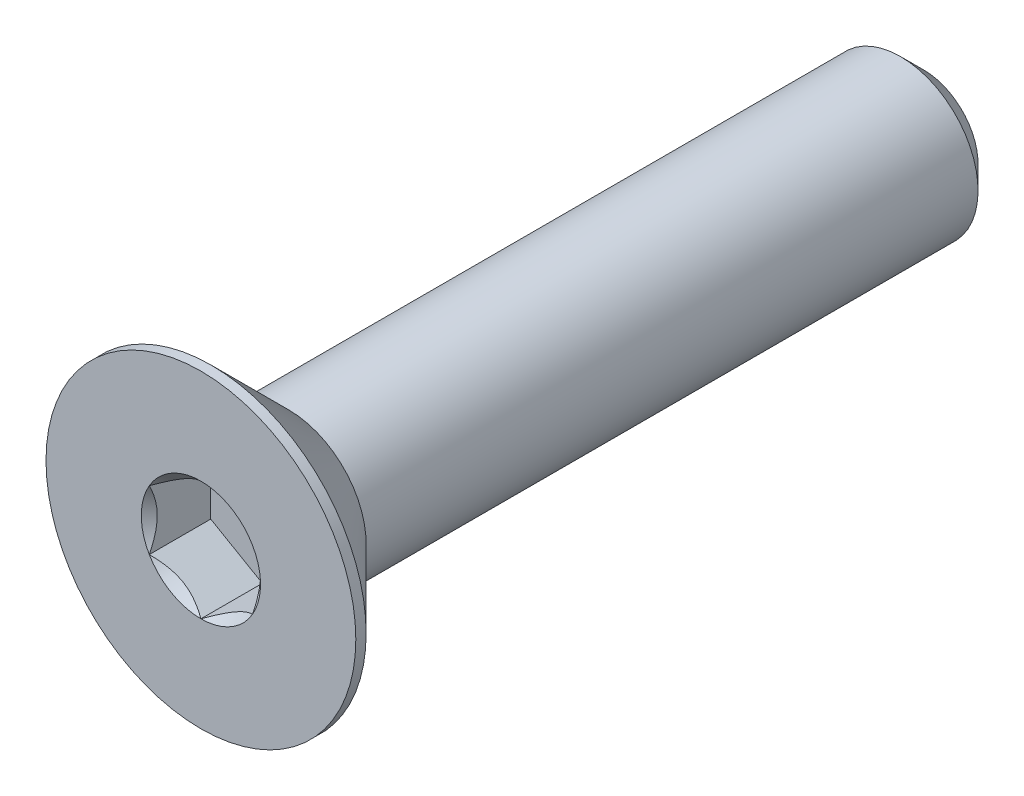
SolidWorks part; units mm, degrees
ref_plane "Front" through (0, 0, 0) normal (0, 0, 1) x (1, 0, 0)
ref_plane "Top" through (0, 0, 0) normal (0, 1, 0) x (1, 0, 0)
ref_plane "Right" through (0, 0, 0) normal (1, 0, 0) x (0, 0, -1)
sketch "Sketch1" plane through (0, 0, 0) normal (1, 0, 0) x (0, 0, -1)
  line L0 (-7, 3) -> (-6.8, 3) construction
  line L1 (-6.8, 3) -> (-5.3, 1.5) construction
  line L2 (-7, 1.5) -> (7, 1.5) construction
  line L3 (7, 1.5) -> (7, 0) construction
  line L4 (7, 0) -> (-7, 0) construction
  line L5 (-7, 0) -> (-7, 3) construction
  line L6 (-7, 3) -> (-7, -3) construction
  line L7 (7, 1.5) -> (7, -1.5) construction
  line L8 (-7, -3) -> (-6.8, -3) construction
  line L9 (-6.8, -3) -> (-5.3, -1.5) construction
  line L11 (-7, 1.5) -> (-7, 0) construction
  line L12 (-5.3, 1.5) -> (-5.3, 0) construction
  line L13 (6.9688, 1.5541) -> (7.2188, 1.1211) construction
  line L14 (7.2188, 1.1211) -> (7.4688, 1.5541) construction
  line L15 (7.4688, 1.5541) -> (6.9688, 1.5541) construction
  line L16 (7.2188, 1.5541) -> (7.2188, 1.5) construction
  line L17 (7.2188, 1.5) -> (7.2188, 1.1752) construction
  line L18 (7.2188, 1.1752) -> (7.2188, 1.1211) construction
  line L19 (7.2188, 1.5271) -> (7.4531, 1.5271) construction
  line L20 (7.2188, 1.5271) -> (6.9844, 1.5271) construction
  line L21 (7, 1.5) -> (7.4375, 1.5) construction
  line L22 (7.1875, 1.1752) -> (7.25, 1.1752) construction
  line L23 (7, -1.5) -> (-5.3, -1.5) construction
  point P10 (5.75, -1.5)
  point P24 (-5.3, 1.5)
  point P30 (0, 0)
  dimension "Head Diameter" = 6
  dimension "Head Height" = 1.7
  dimension "Length" = 14
  dimension "Countersink Angle" = 90
  dimension "Thread Pitch" = 0.5
  dimension "D2" = 0.0625
  dimension "Thread Size" = 3
  dimension "D1" = 1.25
sketch "Sketch2" plane through (0, 0, 0) normal (0, 0, 1) x (1, 0, 0)
  line L1 (0, 1.1547) -> (-1, 0.5774) construction
  line L2 (-1, 0.5774) -> (-1, -0.5774) construction
  line L3 (-1, -0.5774) -> (0, -1.1547) construction
  line L4 (0, -1.1547) -> (1, -0.5774) construction
  line L5 (1, -0.5774) -> (1, 0.5774) construction
  line L6 (1, 0.5774) -> (0, 1.1547) construction
  circle A0 centre (0, 0) radius 1 construction
  dimension "Drive Size" = 2
sketch "Sketch3" plane through (0, 0, 0) normal (1, 0, 0) x (0, 0, -1)
  line L0 (-7, 1.5) -> (7, 1.5)
  line L1 (7, 1.5) -> (7, 0)
  line L2 (7, 0) -> (-7, 0)
  line L3 (-7, 0) -> (-7, 1.5)
revolve "Revolve1" add sketch "Sketch3" angle 360 about L4
chamfer "Chamfer1" distance 0.45 angle 45 1 edges at (0, 1.5, -7)
sketch "Sketch6" plane through (0, 0, 0) normal (1, 0, 0) x (0, 0, -1)
  line L0 (-7, 3) -> (-6.8, 3)
  line L1 (-6.8, 3) -> (-5.3, 1.5)
  line L2 (-5.3, 1.5) -> (-5.3, 0)
  line L3 (-5.3, 0) -> (-7, 0)
  line L4 (-7, 0) -> (-7, 3)
revolve "Revolve2" add sketch "Sketch6" angle 360 about L4
sketch "Sketch8" plane through (0, 0, 7) normal (0, 0, 1) x (1, 0, 0)
  line L0 (0, 1.1547) -> (-1, 0.5774) construction
  line L1 (1, 0.5774) -> (0, 1.1547) construction
  line L2 (1, -0.5774) -> (1, 0.5774) construction
  line L3 (0, -1.1547) -> (1, -0.5774) construction
  line L4 (-1, 0.5774) -> (-1, -0.5774) construction
  line L5 (-1, -0.5774) -> (0, -1.1547) construction
  line L6 (0, 1.1547) -> (-1, 0.5774)
  line L7 (1, 0.5774) -> (0, 1.1547)
  line L8 (1, -0.5774) -> (1, 0.5774)
  line L9 (0, -1.1547) -> (1, -0.5774)
  line L10 (-1, 0.5774) -> (-1, -0.5774)
  line L11 (-1, -0.5774) -> (0, -1.1547)
extrude "Cut-Extrude1" cut sketch "Sketch8" against normal blind 1.19
sketch "Sketch9" plane through (0, 0, 7) normal (0, 0, 1) x (1, 0, 0)
  circle A0 centre (0, 0) radius 1.1547
extrude "Cut-Extrude2" cut sketch "Sketch9" against normal up to next (1.19 mm away) draft 45
ref_plane "Plane1" [suppressed] through (0, 0, 5.3) normal (0, 0, 1) x (1, 0, 0)
split "Split1" [suppressed] bodies to split 124
sketch "Sketch4" plane through (0, 0, -7) normal (0, 0, -1) x (-1, 0, 0)
  circle A0 centre (0, 0) radius 1.5 construction
  circle A1 centre (0, 0) radius 1.5
curve "Helix/Spiral1" [suppressed] pitch 0.5 height 14 turns 28
sketch "Sketch10" plane through (0, 0, 0) normal (1, 0, 0) x (0, 0, -1)
  line L0 (6.9844, 1.5271) -> (7.4531, 1.5271)
  line L1 (7.4531, 1.5271) -> (7.25, 1.1752)
  line L2 (7.25, 1.1752) -> (7.1875, 1.1752)
  line L3 (7.1875, 1.1752) -> (6.9844, 1.5271)
sweep "Cut-Sweep1" [suppressed] cut profiles "Sketch10" path "Helix/Spiral1"
combine bodies "Combine1" [suppressed] operation type add bodies to combine 130 126
equation "\"D2@Sketch1\" = \"Thread Pitch@Sketch1\" / 8"
equation "\"D4@Helix/Spiral1\"=\"Thread Pitch@Sketch1\""
equation "\"D1@Chamfer1\"=\"Thread Size@Sketch1\"*.15"
equation "\"D1@Cut-Extrude1\"=\"Head Height@Sketch1\"*.7"
equation "\"D1@Sketch1\"=\"Thread Pitch@Sketch1\"*2.5"
equation "\"D3@Helix/Spiral1\"=\"Length@Sketch1\""
